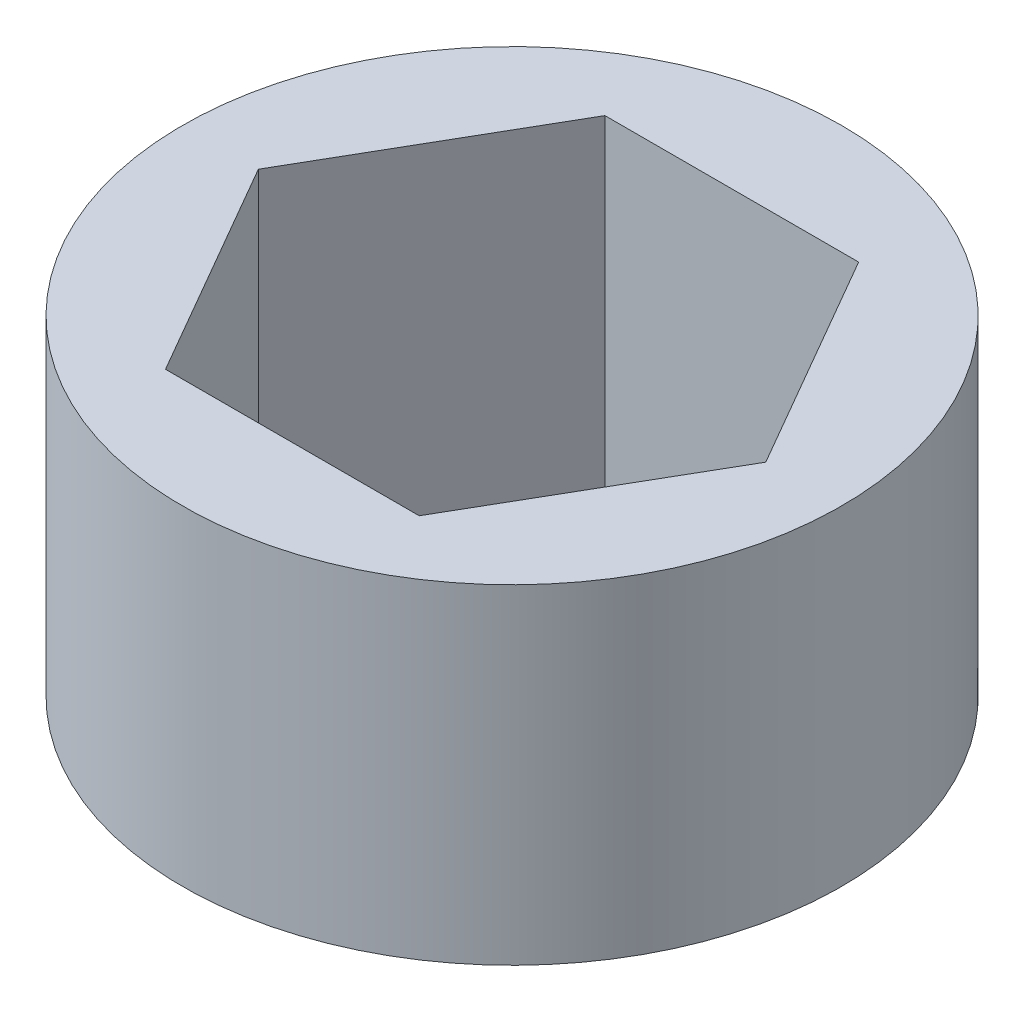
SolidWorks part; units mm, degrees
material "PET"
ref_plane "Front" through (0, 0, 0) normal (0, 0, 1) x (1, 0, 0)
ref_plane "Top" through (0, 0, 0) normal (0, 1, 0) x (1, 0, 0)
ref_plane "Right" through (0, 0, 0) normal (1, 0, 0) x (0, 0, -1)
sketch "Sketch1" plane through (0, 0, 0) normal (0, 1, 0) x (1, 0, 0)
  line L1 (3.6662, 6.35) -> (-3.6662, 6.35)
  line L2 (-3.6662, 6.35) -> (-7.3323, 0)
  line L3 (-7.3323, 0) -> (-3.6662, -6.35)
  line L4 (-3.6662, -6.35) -> (3.6662, -6.35)
  line L5 (3.6662, -6.35) -> (7.3323, 0)
  line L6 (7.3323, 0) -> (3.6662, 6.35)
  circle A0 centre (0, 0) radius 6.35 construction
  circle A2 centre (0, 0) radius 9.525
  point P1 (0, 6.35)
  dimension "D2" = 3.175
  dimension "D1" = 12.7
extrude "Boss-Extrude1" add sketch "Sketch1" along normal blind 9.525
